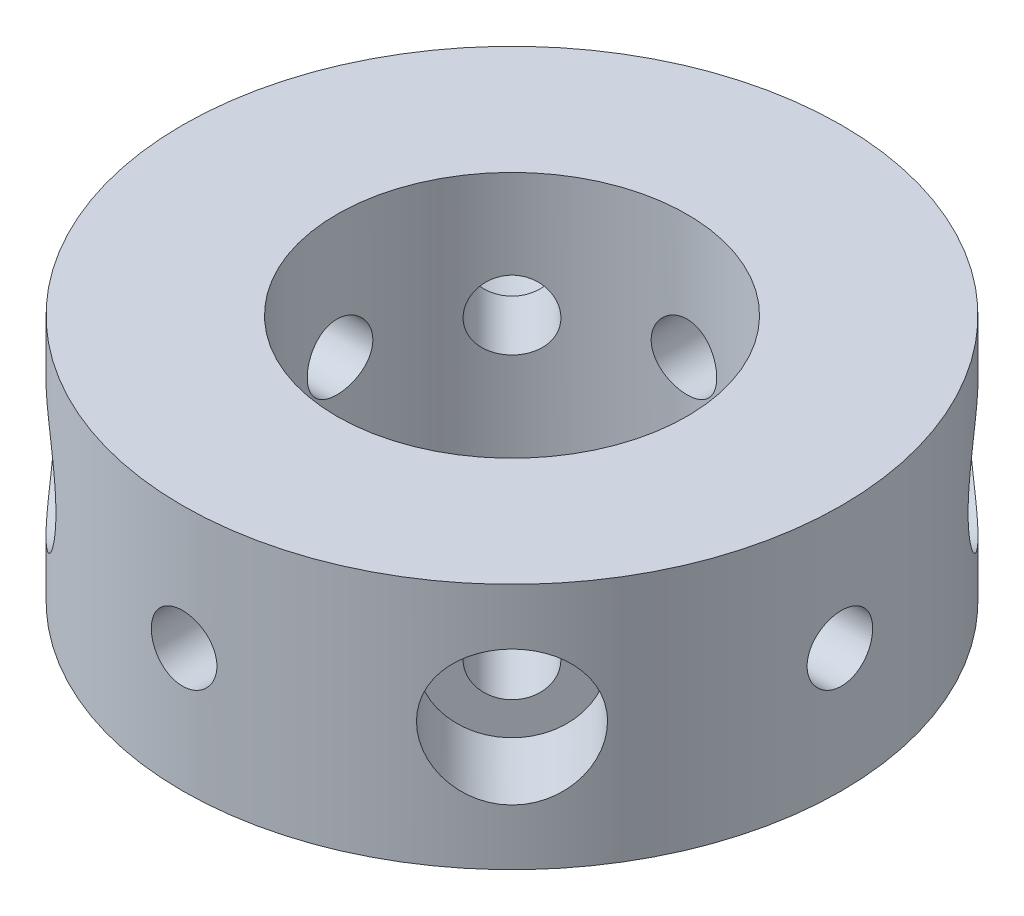
SolidWorks part; units mm, degrees
material "ABS"
ref_plane "Front Plane" through (0, 0, 0) normal (0, 0, 1) x (1, 0, 0)
ref_plane "Top Plane" through (0, 0, 0) normal (0, 1, 0) x (1, 0, 0)
ref_plane "Right Plane" through (0, 0, 0) normal (1, 0, 0) x (0, 0, -1)
sketch "Sketch1" plane through (0, 0, 0) normal (0, 1, 0) x (1, 0, 0)
  line L0 (0, 0) -> (25.4, 0) construction
  line L1 (0, 0) -> (17.9605, -17.9605) construction
  circle A0 centre (0, 0) radius 13.4938
  circle A1 centre (0, 0) radius 27.6225 construction
  circle A2 centre (0, 0) radius 25.4
  dimension "D1" = 26.9875
  dimension "D2" = 55.245
  dimension "D3" = 2.2225
  dimension "D4" = 45
extrude "Boss-Extrude1" add sketch "Sketch1" along normal blind 19.05
ref_plane "Plane1" through (25.4, 0, 0) normal (1, 0, 0) x (0, 0, -1)
ref_plane "Plane2" through (17.9605, 0, 17.9605) normal (0.7071, 0, 0.7071) x (0.7071, 0, -0.7071)
sketch "Sketch2" plane through (25.4, 0, 0) normal (1, 0, 0) x (0, 0, -1)
  line L0 (0, 0) -> (0, 19.05) construction
  line L1 (13.4937, 19.05) -> (-13.4937, 19.05) construction
  point P5 (0, 9.525)
hole_wizard "#8 (0.199) Diameter Hole1" positions "Sketch2" profile "Sketch3" hole size "#8" standard "ANSI Inch" end condition up to next
sketch "Sketch3" plane through (25.4, 9.525, 0) normal (0, 1, 0) x (0, 0, -1)
  line L0 (0, 0) -> (0, 11.9062)
  line L1 (0, 11.9062) -> (2.5273, 11.9062)
  line L2 (2.5273, 11.9062) -> (2.5273, 0)
  line L5 (2.5273, 0) -> (0, 0)
  line L11 (0, -6.35) -> (0, 107.95) construction
  dimension "Thru Hole Dia." = 5.0546
  dimension "Thru Hole Depth" = 11.9062
sketch "Sketch6" plane through (17.9605, 0, 17.9605) normal (0.7071, 0, 0.7071) x (0.7071, 0, -0.7071)
  line L0 (0, 0) -> (0, 19.05) construction
  line L1 (25.4, 19.05) -> (-25.4, 19.05) construction
  circle A0 centre (0, 9.525) radius 5.207
  circle A1 centre (0, 9.525) radius 2.667
  dimension "D1" = 2.54
  dimension "D2" = 5.334
extrude "bulkhead_through" cut sketch "Sketch6" against normal up to next contours A1
extrude "access_hole" cut sketch "Sketch6<4>" against normal blind 6.35 contours A0
sketch "Sketch6<4>" plane through (17.9605, 0, 17.9605) normal (0.7071, 0, 0.7071) x (0.7071, 0, -0.7071) same geometry as "Sketch6"
pattern_circular "CirPattern1" count 4 over 360 about axis through (0, 19.05, 0) along (0, -1, 0) of "#8 (0.199) Diameter Hole1", "access_hole", "bulkhead_through"
